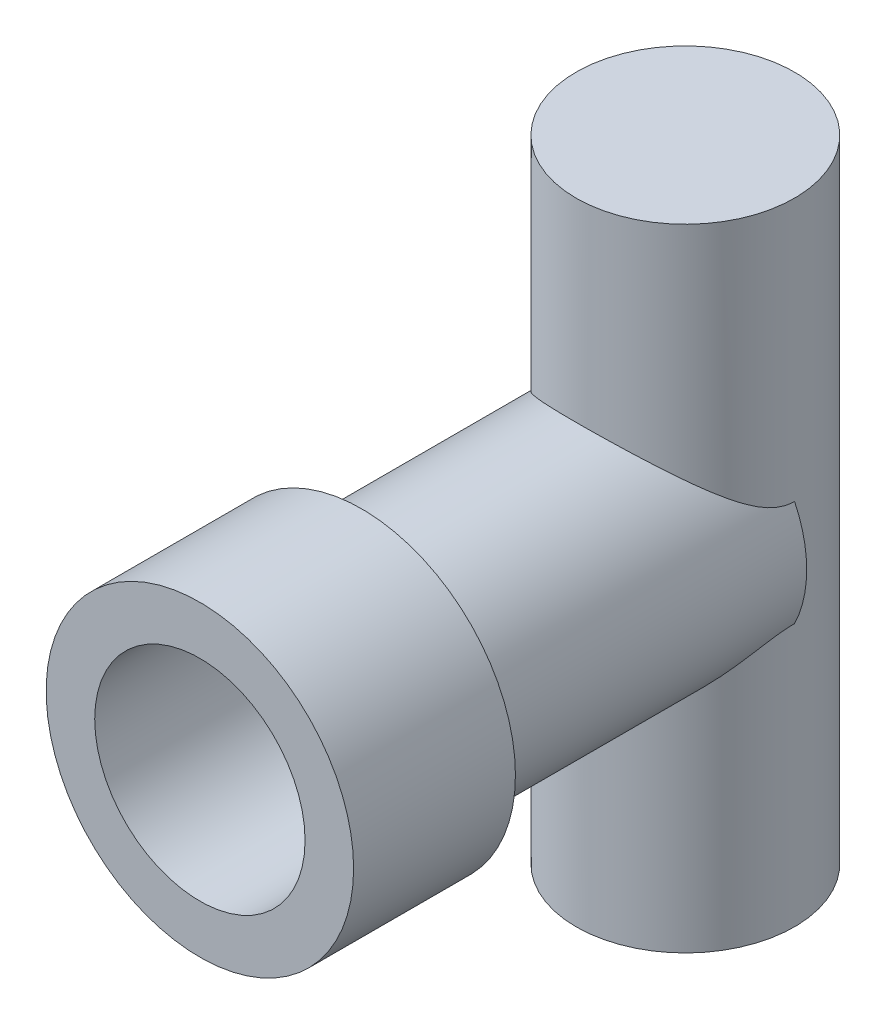
SolidWorks part; units mm, degrees
ref_plane "前视基准面" through (0, 0, 0) normal (0, 0, 1) x (1, 0, 0)
ref_plane "上视基准面" through (0, 0, 0) normal (0, 1, 0) x (1, 0, 0)
ref_plane "右视基准面" through (0, 0, 0) normal (1, 0, 0) x (0, 0, -1)
other "Configuration Table"
sketch "草图1" plane through (0, 0, 0) normal (0, 0, 1) x (1, 0, 0)
  circle A0 centre (0, 0) radius 26
  circle A1 centre (0, 0) radius 30
extrude "凸台-拉伸1" add sketch "草图1" against normal blind 120
sketch "草图2" plane through (0, 0, 0) normal (0, 0, 1) x (1, 0, 0)
  circle A0 centre (0, 0) radius 30
  circle A1 centre (0, 0) radius 38
extrude "凸台-拉伸2" add sketch "草图2" against normal blind 40
sketch "草图3" plane through (0, 0, 0) normal (0, 1, 0) x (1, 0, 0)
  line L0 (26, 120) -> (-26, 120) construction
  circle A0 centre (0, 120) radius 27
extrude "凸台-拉伸3" add sketch "草图3" along normal blind 78 and the other way blind 78
